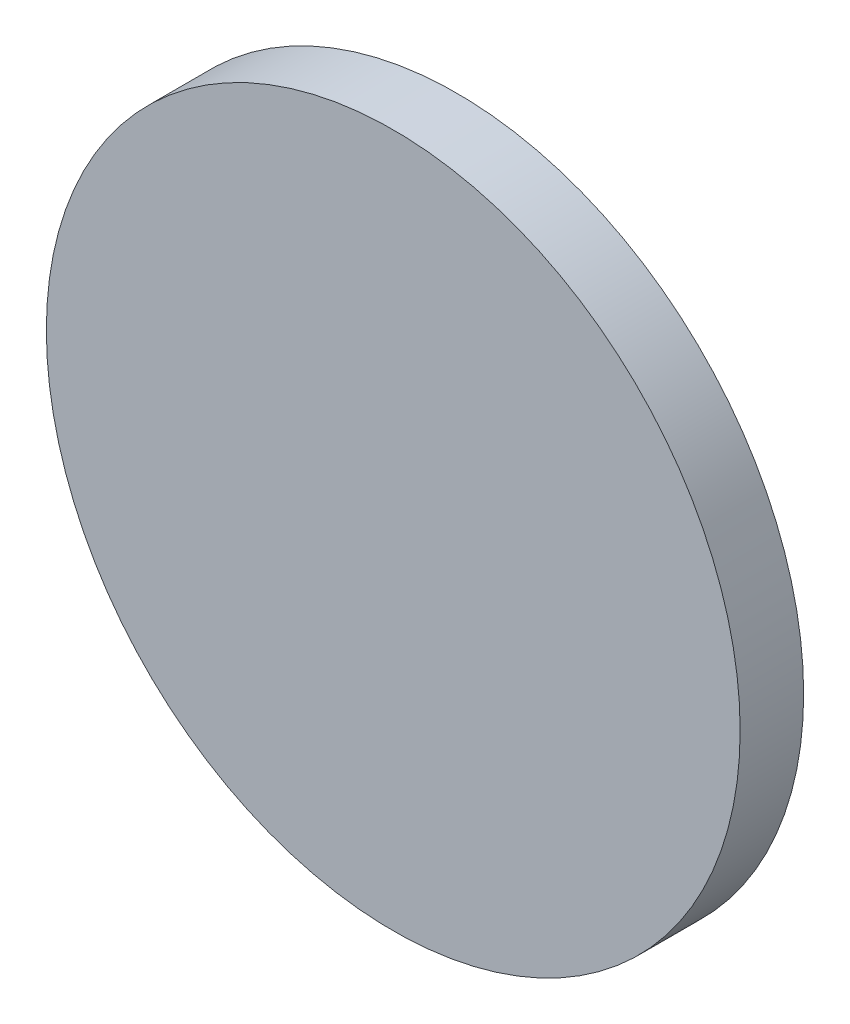
SolidWorks part; units mm, degrees
ref_plane "Front Plane" through (0, 0, 0) normal (0, 0, 1) x (1, 0, 0)
ref_plane "Top Plane" through (0, 0, 0) normal (0, 1, 0) x (1, 0, 0)
ref_plane "Right Plane" through (0, 0, 0) normal (1, 0, 0) x (0, 0, -1)
sketch "Sketch1" plane through (0, 0, 0) normal (0, 0, 1) x (1, 0, 0)
  line L0 (0, 0) -> (0, 25.4) construction
  line L1 (0, 0) -> (21.997, -12.7) construction
  line L2 (0, 0) -> (-21.997, -12.7) construction
  circle A0 centre (0, 25.4) radius 1.905
  circle A1 centre (21.997, -12.7) radius 1.905
  circle A2 centre (-21.997, -12.7) radius 1.905
  circle A3 centre (0, 0) radius 34.6944
  point P7 (0, 0)
  dimension "D3" = 3.81
  dimension "D1" = 25.4
  dimension "D2" = 3
extrude "Boss-Extrude1" add sketch "Sketch1" along normal blind 6.35 contours A0 | A2 | A1 | A3 A0 A1 A2 region at (0, 25.4, 0) region at (21.997, -12.7, 0) region at (-21.997, -12.7, 0) region at (0, 0, 0)
